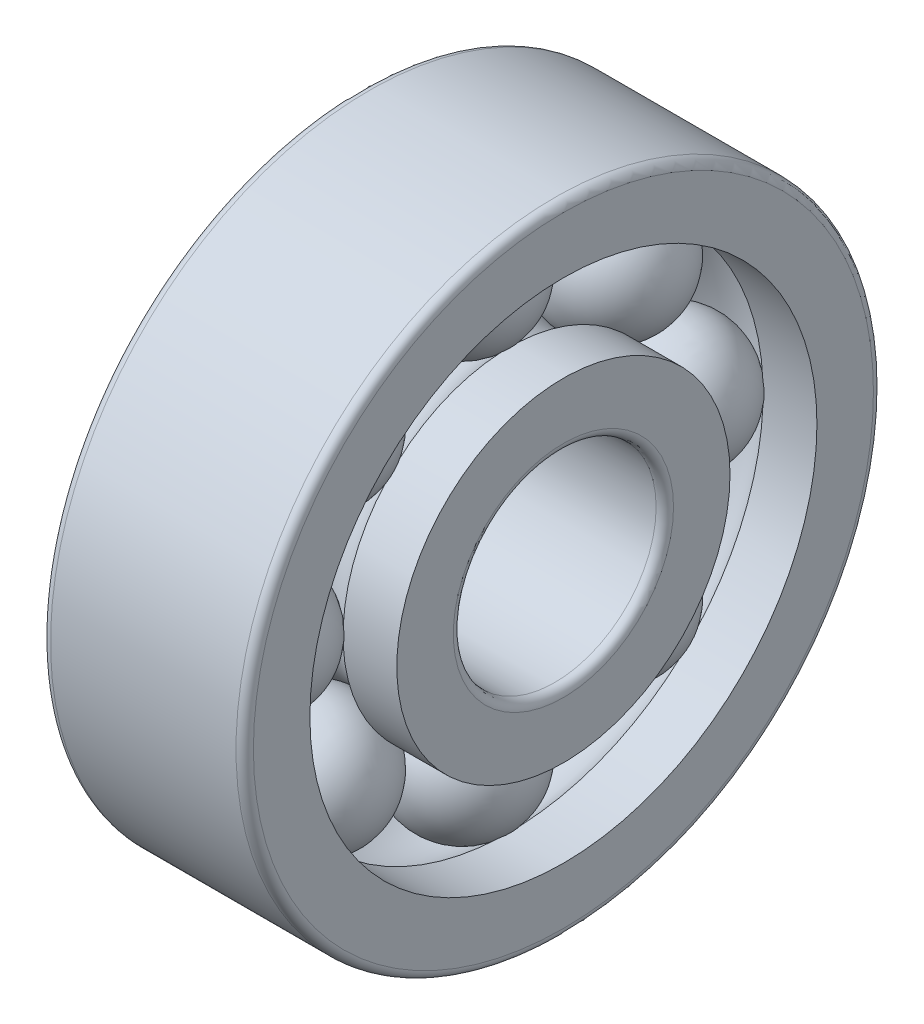
SolidWorks part; units mm, degrees
ref_plane "Plane1" through (0, 0, 0) normal (0, 0, 1) x (1, 0, 0)
ref_plane "Plane2" through (0, 0, 0) normal (0, 1, 0) x (1, 0, 0)
ref_plane "Plane3" through (0, 0, 0) normal (1, 0, 0) x (0, 0, -1)
sketch "Clipboard" plane through (0, 0, 0) normal (0, 0, 1) x (1, 0, 0)
  line L0 (-10, 0) -> (10, 0) construction
  line L1 (0, 0) -> (22.1431, -3.112)
  line L2 (0, 0) -> (7.1794, 1.009)
  line L3 (0, 0) -> (22.1431, -3.112)
  line L4 (0, 0) -> (-22.3573, -0.3902)
  dimension "BallCLRad" = 7.25
sketch "CagSpiSke" plane through (0, 0, 0) normal (0, 0, 1) x (1, 0, 0)
  line L0 (0.225, 6.875) -> (0.225, 7.625)
  line L1 (0.225, 7.625) -> (-0.225, 7.625)
  line L2 (-0.225, 7.625) -> (-0.225, 6.875)
  line L3 (-0.225, 6.875) -> (0.225, 6.875)
  line L4 (-20.6375, 0) -> (20.6375, 0) construction
  line L5 (0, 0) -> (0, 23.7692) construction
  dimension "OD" = 15.25
  dimension "ID" = 13.75
revolve "CageSpine" add sketch "CagSpiSke" angle 0.001 about L4 reverse direction yes
ref_axis "Axis1" through (-50, 0, 0) along (1, 0, 0)
sketch "CagBalSke" plane through (0, 0, 0) normal (0, 0, 1) x (1, 0, 0)
  line L0 (-2.475, 7.25) -> (2.475, 7.25)
  line L1 (-1.905, 7.25) -> (1.905, 7.25) construction
  line L2 (-10, 0) -> (10, 0) construction
  line L3 (0, 0) -> (0, 24) construction
  arc A0 (2.475, 7.25) -> (-2.475, 7.25) centre (0, 7.25) cw
  dimension "BallCLRad" = 7.25
revolve "CageBall" [suppressed] add sketch "CagBalSke" angle 360 about L1 reverse direction yes
pattern_circular "CageBalls" [suppressed] count 8 every 45 about axis through (-50, 0, 0) along (1, 0, 0)
sketch "CagTrmODSke" plane through (0, 0, 0) normal (0, 0, 1) x (1, 0, 0)
  line L0 (2.476, 7.625) -> (2.476, 9.726)
  line L1 (2.476, 9.726) -> (-2.476, 9.726)
  line L2 (-2.476, 9.726) -> (-2.476, 7.625)
  line L3 (-2.476, 7.625) -> (2.476, 7.625)
  line L4 (-20.6375, 0) -> (20.6375, 0) construction
  line L5 (0, 0) -> (0, 25) construction
  dimension "Width" = 4.952
  dimension "ID" = 15.25
  dimension "OD" = 19.452
revolve "CageTrimOD" [suppressed] cut sketch "CagTrmODSke" angle 360 about L4 reverse direction yes
sketch "CagTrmIDSke" plane through (0, 0, 0) normal (0, 0, 1) x (1, 0, 0)
  line L0 (2.476, 4.776) -> (2.476, 6.875)
  line L1 (2.476, 6.875) -> (-2.476, 6.875)
  line L2 (-2.476, 6.875) -> (-2.476, 4.776)
  line L3 (-2.476, 4.776) -> (2.476, 4.776)
  line L4 (-20.6375, 0) -> (20.6375, 0) construction
  line L5 (0, 0) -> (0, 25) construction
  dimension "Width" = 4.952
  dimension "ID" = 9.552
  dimension "OD" = 13.75
revolve "CageTrimID" [suppressed] cut sketch "CagTrmIDSke" angle 360 about L4 reverse direction yes
sketch "BalSimSke" plane through (0, 0, 0) normal (0, 0, 1) x (1, 0, 0)
  line L0 (-10, 0) -> (10, 0) construction
  line L1 (-10, 7.25) -> (10, 7.25) construction
  line L2 (0, 0) -> (0, 23) construction
  circle A0 centre (0, 7.25) radius 2.25
  dimension "BallCLRad" = 7.25
  dimension "Ball_diameter" = 4.5
revolve "BallsSimplified" [suppressed] add sketch "BalSimSke" angle 360 about L0
sketch "BalDetSke" plane through (0, 0, 0) normal (0, 0, 1) x (1, 0, 0)
  line L0 (-2.25, 7.25) -> (2.25, 7.25)
  line L1 (-1.905, 7.25) -> (1.905, 7.25) construction
  line L2 (0, 0) -> (0, 25) construction
  arc A0 (2.25, 7.25) -> (-2.25, 7.25) centre (0, 7.25) cw
  dimension "BallCLRad" = 7.25
  dimension "Ball_diameter" = 4.5
revolve "BallDetailed" add sketch "BalDetSke" angle 360 about L1 reverse direction yes
sketch "InnRacSke" plane through (0, 0, 0) normal (0, 0, 1) x (1, 0, 0)
  line L0 (-1.6434, 5.75) -> (-3.5, 5.75)
  line L1 (-3.5, 5.75) -> (-3.5, 3.8)
  line L2 (-3.2, 3.5) -> (3.2, 3.5)
  line L3 (3.5, 3.8) -> (3.5, 5.75)
  line L4 (3.5, 5.75) -> (1.6434, 5.75)
  line L5 (-20.6375, 0) -> (20.6375, 0) construction
  line L6 (0, 0) -> (0, 30) construction
  arc A0 (-3.5, 3.8) -> (-3.2, 3.5) centre (-3.2, 3.8) ccw
  arc A1 (3.2, 3.5) -> (3.5, 3.8) centre (3.2, 3.8) ccw
  arc A2 (1.6434, 5.75) -> (-1.6434, 5.75) centre (0, 7.25) cw
  dimension "BallCLRad" = 7.25
  dimension "Fillet_radius" = 0.3
  dimension "Ball_diameter" = 4.45
  dimension "ID" = 7
  dimension "OD" = 11.5
  dimension "Width" = 7
revolve "InnerRace" add sketch "InnRacSke" angle 360 about L5 reverse direction yes
sketch "OutRacSke" plane through (0, 0, 0) normal (0, 0, 1) x (1, 0, 0)
  line L0 (-1.6434, 8.75) -> (-3.5, 8.75)
  line L1 (-3.5, 8.75) -> (-3.5, 10.7)
  line L2 (-3.2, 11) -> (3.2, 11)
  line L3 (3.5, 10.7) -> (3.5, 8.75)
  line L4 (3.5, 8.75) -> (1.6434, 8.75)
  line L5 (-20.6375, 0) -> (20.6375, 0) construction
  line L6 (0, 0) -> (0, 30) construction
  arc A0 (-3.5, 10.7) -> (-3.2, 11) centre (-3.2, 10.7) cw
  arc A1 (3.2, 11) -> (3.5, 10.7) centre (3.2, 10.7) cw
  arc A2 (1.6434, 8.75) -> (-1.6434, 8.75) centre (0, 7.25) ccw
  dimension "BallCLRad" = 7.25
  dimension "Fillet_radius" = 0.3
  dimension "Ball_diameter" = 4.45
  dimension "Width" = 7
revolve "OuterRace" add sketch "OutRacSke" angle 360 about L5 reverse direction yes
pattern_circular "BallsDetailed" count 8 every 45 about axis through (-50, 0, 0) along (1, 0, 0) of "BallDetailed"
equation "\"BallCLRad@Clipboard\" = ( \"OD@OutRacSke\" + \"ID@InnRacSke\" ) / 4"
equation "\"BallCLRad@BalSimSke\" = \"BallCLRad@Clipboard\""
equation "\"BallCLRad@BalDetSke\" = \"BallCLRad@Clipboard\""
equation "\"BallCLRad@InnRacSke\" = \"BallCLRad@Clipboard\""
equation "\"BallCLRad@OutRacSke\" = \"BallCLRad@Clipboard\""
equation "\"Ball_diameter@InnRacSke\" = \"Ball_diameter@BalDetSke\" - 0.05"
equation "\"Ball_diameter@OutRacSke\" = \"Ball_diameter@BalDetSke\" - 0.05"
equation "\"Ball_diameter@BalSimSke\" = \"Ball_diameter@BalDetSke\""
equation "\"Width@OutRacSke\" = \"Width@InnRacSke\""
equation "\"Fillet_radius@OutRacSke\" = \"Fillet_radius@InnRacSke\""
equation "\"Max_count@Clipboard\" = int( 3.14159265 / atn(( \"Ball_diameter@BalDetSke\" / 2) / sqr( \"BallCLRad@Clipboard\"  *  \"BallCLRad@Clipboard\" - ( \"Ball_diameter@BalDetSke\" / 2) *  ( \"Ball_diameter@BalDetSke\" / 2))))"
equation "\"Max_count@Clipboard\" = ((sgn( \"Max_count@Clipboard\" - \"Count@Clipboard\" )-1)*( \"Max_count@Clipboard\" - \"Count@Clipboard\" ))/-2+ \"Count@Clipboard\""
equation "\"Count@BallsDetailed\" = int( \"Show_count@Clipboard\" ) "
equation "\"Count@BallsDetailed\" = ((sgn( \"Count@BallsDetailed\" - \"Max_count@Clipboard\" )-1)*( \"Count@BallsDetailed\" - \"Max_count@Clipboard\" ))/-2+ \"Max_count@Clipboard\""
equation "\"Count@BallsDetailed\" = ((sgn( \"Count@BallsDetailed\" - \"Min_count@Clipboard\" )+1)*( \"Count@BallsDetailed\" - \"Min_count@Clipboard\"))/2 +\"Min_count@Clipboard\""
equation "\"Angle@BallsDetailed\" = 360.0 / \"Max_count@Clipboard\""
equation "\"BallCLRad@CagBalSke\" = \"BallCLRad@Clipboard\""
equation "\"Count@CageBalls\" = \"Count@BallsDetailed\""
equation "\"Angle@CageBalls\" = \"Angle@BallsDetailed\""
equation "\"Angle@CageSpine\" =  \"Angle@CageBalls\" * ( \"Count@CageBalls\" -1 + int( \"Count@CageBalls\" / \"Max_count@Clipboard\" ) )  + 0.001 -  int( \"Count@CageBalls\" / \"Max_count@Clipboard\" ) * 0.001"
equation "\"Angle@CageSpine\" =  \"Angle@CageSpine\" * int( \"Min_count@Clipboard\" / 2) + int(1 / \"Min_count@Clipboard\")  * 0.001"
equation "\"CageWallOD@CagBalSke\" =  \"Ball_diameter@BalDetSke\" * 1.1"
equation "\"Thickness@CagSpiSke\" =  \"Ball_diameter@BalDetSke\" * 0.1"
equation "\"OD@CagTrmODSke\" = \"BallCLRad@Clipboard\" * 2 + \"CageWallOD@CagBalSke\" + 0.002"
equation "\"ID@CagTrmODSke\" = \"BallCLRad@Clipboard\" * 2 + \"Ball_diameter@BalDetSke\" / 6"
equation "\"OD@CagTrmIDSke\" = \"BallCLRad@Clipboard\" * 2 - \"Ball_diameter@BalDetSke\" / 6"
equation "\"ID@CagTrmIDSke\" = \"BallCLRad@Clipboard\" * 2 - \"CageWallOD@CagBalSke\" + 0.002"
equation "\"OD@CagSpiSke\" = \"ID@CagTrmODSke\""
equation "\"ID@CagSpiSke\" = \"OD@CagTrmIDSke\""
equation "\"Width@CagTrmODSke\" = \"CageWallOD@CagBalSke\" + 0.002"
equation "\"Width@CagTrmIDSke\" = \"CageWallOD@CagBalSke\" + 0.002"
